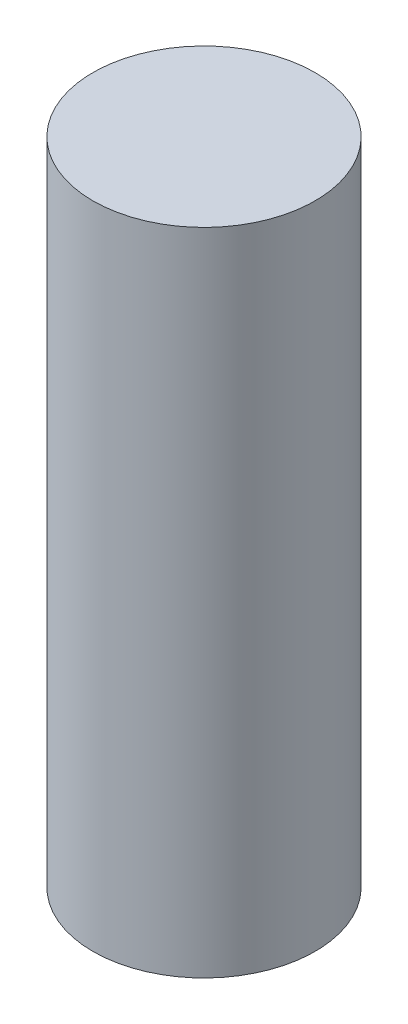
SolidWorks part; units mm, degrees
ref_plane "Front Plane" through (0, 0, 0) normal (0, 0, 1) x (1, 0, 0)
ref_plane "Top Plane" through (0, 0, 0) normal (0, 1, 0) x (1, 0, 0)
ref_plane "Right Plane" through (0, 0, 0) normal (1, 0, 0) x (0, 0, -1)
sketch "Sketch1" plane through (0, 0, 0) normal (0, 1, 0) x (1, 0, 0)
  circle A0 centre (0, 0) radius 2
  dimension "D1" = 4
extrude "Boss-Extrude1" add sketch "Sketch1" along normal blind 11.7
